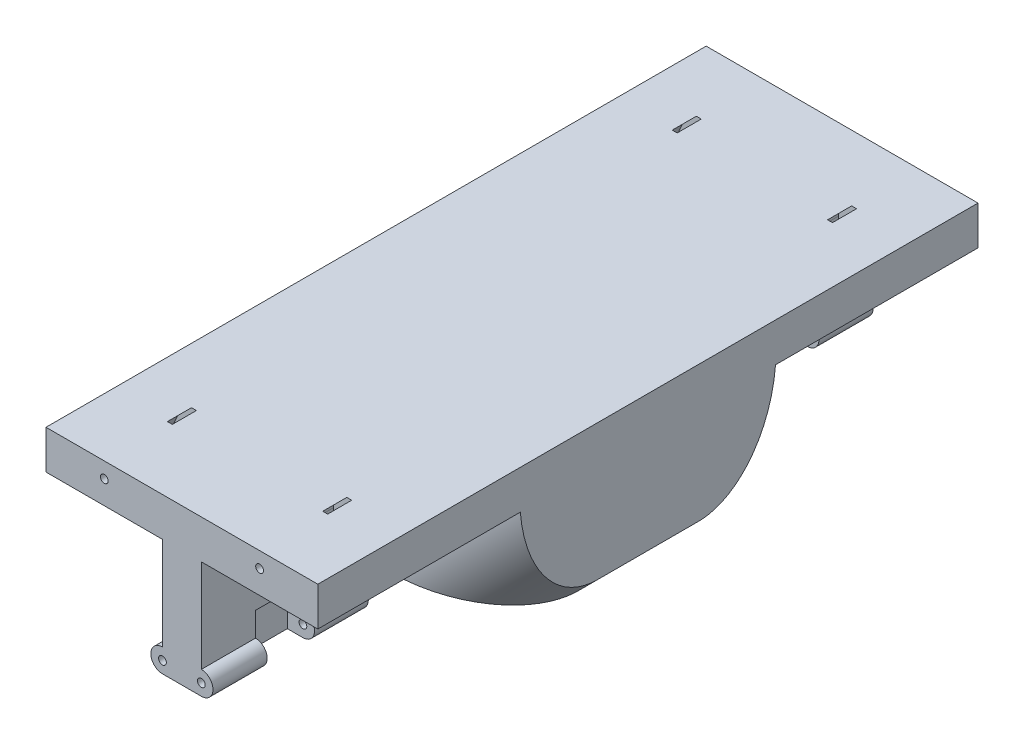
SolidWorks part; units mm, degrees
material "ABS"
ref_plane "Спереди" through (0, 0, 0) normal (0, 0, 1) x (1, 0, 0)
ref_plane "Сверху" through (0, 0, 0) normal (0, 1, 0) x (1, 0, 0)
ref_plane "Справа" through (0, 0, 0) normal (1, 0, 0) x (0, 0, -1)
sketch "Эскиз1" plane through (0, 0, 0) normal (0, 0, 1) x (1, 0, 0)
  line L0 (0, 30.7154) -> (0, -31.2898) construction
  line L2 (35, -20.2872) -> (-35, -20.2872)
  line L3 (35, -20.2872) -> (35, 19.7128)
  line L4 (35, 19.7128) -> (-35, 19.7128)
  line L5 (-35, -20.2872) -> (-35, 19.7128)
  line L6 (35, -20.2872) -> (-35, 19.7128) construction
  line L7 (35, 19.7128) -> (-35, -20.2872) construction
  point P3 (0, -0.2872)
  dimension "D1" = 70
  dimension "D2" = 40
extrude "Бобышка-Вытянуть1" add sketch "Эскиз1" along normal mid plane 170
sketch "Эскиз7" plane through (0, 0, 85) normal (0, 0, 1) x (1, 0, 0)
  line L0 (0, 19.7128) -> (0, -20.2872) construction
  line L1 (-35, -20.2872) -> (-5, -20.2872)
  line L2 (-35, -20.2872) -> (-35, 9.7128)
  line L3 (-35, 9.7128) -> (-5, 9.7128)
  line L4 (-5, -20.2872) -> (-5, 9.7128)
  line L5 (35, 19.7128) -> (-35, 19.7128) construction
  line L6 (-35, -20.2872) -> (35, -20.2872) construction
  dimension "D1" = 30
  dimension "D2" = 5
extrude "Вырез-Вытянуть5" cut sketch "Эскиз7" against normal blind 52
sketch "Эскиз4" plane through (0, 0, 85) normal (0, 0, 1) x (1, 0, 0)
  line L0 (-27.9128, 0) -> (25.9263, 0) construction
  line L1 (-5, -20.2872) -> (-5, 9.7128) construction
  line L2 (-35, -20.2872) -> (-5, -20.2872) construction
  circle A1 centre (-5, -17.2872) radius 3
  dimension "D1" = 6
  dimension "D3" = 3
extrude "Бобышка-Вытянуть3" add sketch "Эскиз4" against normal blind 40
sketch "Эскиз5" plane through (-5, 0, 0) normal (-1, 0, 0) x (0, 0, 1)
  line L0 (85, -14.2872) -> (85, 9.7128) construction
  line L5 (45, -20.2872) -> (85, -20.2872) construction
  line L6 (58.85, -20.2872) -> (71.05, -20.2872)
  line L11 (58.85, -20.2872) -> (58.85, -8.0872)
  line L12 (58.85, -8.0872) -> (71.05, -8.0872)
  line L13 (71.05, -20.2872) -> (71.05, -8.0872)
  dimension "D4" = 12.2
  dimension "D1" = 13.95
  dimension "D2" = 12.2
extrude "Вырез-Вытянуть3" cut sketch "Эскиз5" against normal mid plane 8
sketch "Эскиз6" plane through (0, 0, 85) normal (0, 0, 1) x (1, 0, 0)
  circle A1 centre (-5, -17.2872) radius 1
  arc A2 (-5, -14.2872) -> (-5, -20.2872) centre (-5, -17.2872) ccw construction
  dimension "D1" = 2
extrude "Вырез-Вытянуть4" cut sketch "Эскиз6" against normal blind 40
mirror "Зеркальное отражение1" about plane through (0, 0, 0) normal (0, 0, 1) of "Вырез-Вытянуть5", "Вырез-Вытянуть4", "Вырез-Вытянуть3", "Бобышка-Вытянуть3"
mirror "Зеркальное отражение2" about plane through (0, 0, 0) normal (1, 0, 0) of "Зеркальное отражение1"
sketch "Эскиз9" plane through (0, 0, 0) normal (0, 0, 1) x (1, 0, 0)
  line L0 (0, 19.7128) -> (0, -20.2872) construction
  line L3 (-5, -16.2872) -> (-5, -18.2872) construction
  line L4 (5, -16.2872) -> (5, -18.2872) construction
  line L5 (-2, 20.7128) -> (-2, -13.2872)
  line L6 (-0.101, -16.2872) -> (0.101, -16.2872)
  line L7 (2, -13.2872) -> (2, 20.7128)
  line L8 (-0.101, 15.7128) -> (0.101, 15.7128)
  line L9 (35, 19.7128) -> (-35, 19.7128) construction
  line L10 (-5, -14.2872) -> (-5, 9.7128) construction
  line L11 (-5, -20.2872) -> (5, -20.2872) construction
  line L13 (-5, 19.7128) -> (-35, 19.7128) construction
  line L14 (-5, -20.2872) -> (-5, 9.7128) construction
  line L15 (35, 19.7128) -> (-35, 19.7128) construction
  circle A0 centre (-5, 16.7128) radius 5
  circle A1 centre (5, 16.7128) radius 5
  circle A2 centre (-5, -17.2872) radius 5
  circle A3 centre (5, -17.2872) radius 5
  dimension "D1" = 10
  dimension "D2" = 4
  dimension "D3" = 3
  dimension "D4" = 4
  dimension "D5" = 3
extrude "Вырез-Вытянуть7" [suppressed] cut sketch "Эскиз9" against normal through all both and the other way through all contours L0 L8 A0 L5 A2 L6 | L8 L0 L6 A3 L7 A1
sketch "Эскиз10" plane through (0, 0, 33) normal (0, 0, 1) x (1, 0, 0)
  line L0 (35, 9.7128) -> (35, -20.2872) construction
  line L2 (-5, -20.2872) -> (5, -20.2872) construction
  line L4 (-35, 9.7128) -> (-35, -20.2872) construction
  line L5 (35, 9.7128) -> (35, -15.2872)
  line L6 (-35, -15.2872) -> (-30, -20.2872)
  line L7 (-30, -20.2872) -> (30, -20.2872)
  line L8 (35, -15.2872) -> (30, -20.2872)
  line L9 (-35, 9.7128) -> (-35, -15.2872)
  line L10 (-35, -15.2872) -> (-35, -20.2872)
  line L11 (-35, -20.2872) -> (-30, -20.2872)
  line L12 (30, -20.2872) -> (35, -20.2872)
  line L13 (35, -20.2872) -> (35, -15.2872)
  line M4 (-35, 9.7128) -> (-35, -20.2872)
  line M5 (-35, -20.2872) -> (-5, -20.2872)
extrude "Вырез-Вытянуть8" cut sketch "Эскиз10" against normal up to next contours L6 M4 M5 | L12 L13 L8 region at (33.3333, -18.6205, 33) region at (-33.3333, -18.6205, 33)
sketch "Эскиз11" [suppressed] plane through (0, 9.7128, 0) normal (0, -1, 0) x (1, 0, 0)
  line L2 (-0.101, 65) -> (0, -65) construction
  line L3 (-5, -65) -> (5, -65) construction
  line L4 (-35, 0) -> (35, 0) construction
  line L5 (-35, -13) -> (-35, 13) construction
  line L6 (35, -13) -> (35, 13) construction
  circle A0 centre (-24.0855, 45) radius 3
  dimension "D1" = 6
  dimension "D2" = 45
  dimension "D3" = 24
extrude "Вырез-Вытянуть9" [suppressed] cut sketch "Эскиз11" against normal blind 4
sketch "Эскиз12" [suppressed] plane through (0, 13.7128, 0) normal (0, -1, 0) x (1, 0, 0)
  circle A0 centre (-24.0855, 45) radius 1.5
  dimension "D1" = 3
extrude "Вырез-Вытянуть10" [suppressed] cut sketch "Эскиз12" against normal up to surface (6 mm away) up to face at (0, 19.7128, 0)
mirror "Зеркальное отражение3" [suppressed] about plane through (0, 0, 0) normal (1, 0, 0)
mirror "Зеркальное отражение4" [suppressed] about plane through (0, 0, 0) normal (0, 0, 1)
sketch "Эскиз13" plane through (0, 0, 85) normal (0, 0, 1) x (1, 0, 0)
  line L0 (0, 19.7128) -> (0, -20.2872) construction
  line L1 (35, 19.7128) -> (-35, 19.7128) construction
  line L2 (-5, -20.2872) -> (5, -20.2872) construction
  circle A0 centre (-20, 15.7128) radius 1
  circle A1 centre (20, 15.7128) radius 1
  dimension "D1" = 2
  dimension "D2" = 40
  dimension "D3" = 4
extrude "Вырез-Вытянуть11" cut sketch "Эскиз13" against normal blind 40
ref_plane "Плоскость1" through (0, 0, 65) normal (0, 0, 1) x (1, 0, 0)
sketch "Эскиз14" plane through (0, 0, 65) normal (0, 0, 1) x (1, 0, 0)
  line L0 (-23.7186, 17.3174) -> (-27, 9.7128)
  line L1 (-5, 9.7128) -> (-35, 9.7128) construction
  line L2 (-27, 9.7128) -> (-15.95, 9.7128)
  line L3 (-5, 9.7128) -> (-35, 9.7128) construction
  line L4 (-15.95, 9.7128) -> (-15.95, 15.7128)
  line L5 (-20, 15.7128) -> (-20, 9.7128) construction
  circle A0 centre (-20, 15.7128) radius 4.05
  circle A1 centre (-20, 15.7128) radius 1 construction
  circle A2 centre (-20, 15.7128) radius 1
  dimension "D1" = 8.1
  dimension "D2" = 7
extrude "Вырез-Вытянуть12" cut sketch "Эскиз14" against normal mid plane 6.2 contours L5 A0 L0 L2 | A0 L5 L2 L4 | A2 A0 region at (-23.6201, 11.6177, 65) region at (-19.2039, 19.5669, 65) region at (-17.6296, 11.2673, 65)
sketch "Эскиз15" [suppressed] plane through (-35, 0, 0) normal (-1, 0, 0) x (0, 0, 1)
  line L0 (64.95, -8.0872) -> (64.95, 19.7128) construction
  line L1 (58.85, -8.0872) -> (71.05, -8.0872) construction
  line L2 (85, 19.7128) -> (-85, 19.7128) construction
  line L3 (58.85, -14.2872) -> (71.05, -14.2872) construction
  line L4 (43.784, 9.7128) -> (86.116, 9.7128)
  line L5 (33, 9.7128) -> (85, 9.7128) construction
  circle A0 centre (64.95, -14.2872) radius 32
  line M6 (33, 9.7128) -> (85, 9.7128)
  dimension "D1" = 64
extrude "Вырез-Вытянуть13" [suppressed] cut sketch "Эскиз15" against normal blind 4 contours L0 A0 M6 | L0 L4 A0
fillet "Скругление2" [suppressed] radius 10
fillet "Скругление1" radius 20 4 edges at (-32.5, -17.7872, 33) (-32.5, -17.7872, -33) (32.5, -17.7872, 33) (32.5, -17.7872, -33)
mirror "Зеркальное отражение5" about plane through (0, 0, 0) normal (1, 0, 0) of "Скругление2", "Вырез-Вытянуть13", "Вырез-Вытянуть12", "Вырез-Вытянуть11"
mirror "Зеркальное отражение6" about plane through (0, 0, 0) normal (0, 0, 1) of "Вырез-Вытянуть11", "Вырез-Вытянуть12", "Зеркальное отражение5"
equation "\"D4@Эскиз5\"=\"D2@Эскиз5\""
equation "\"D4@Эскиз9\"=\"D2@Эскиз9\""
